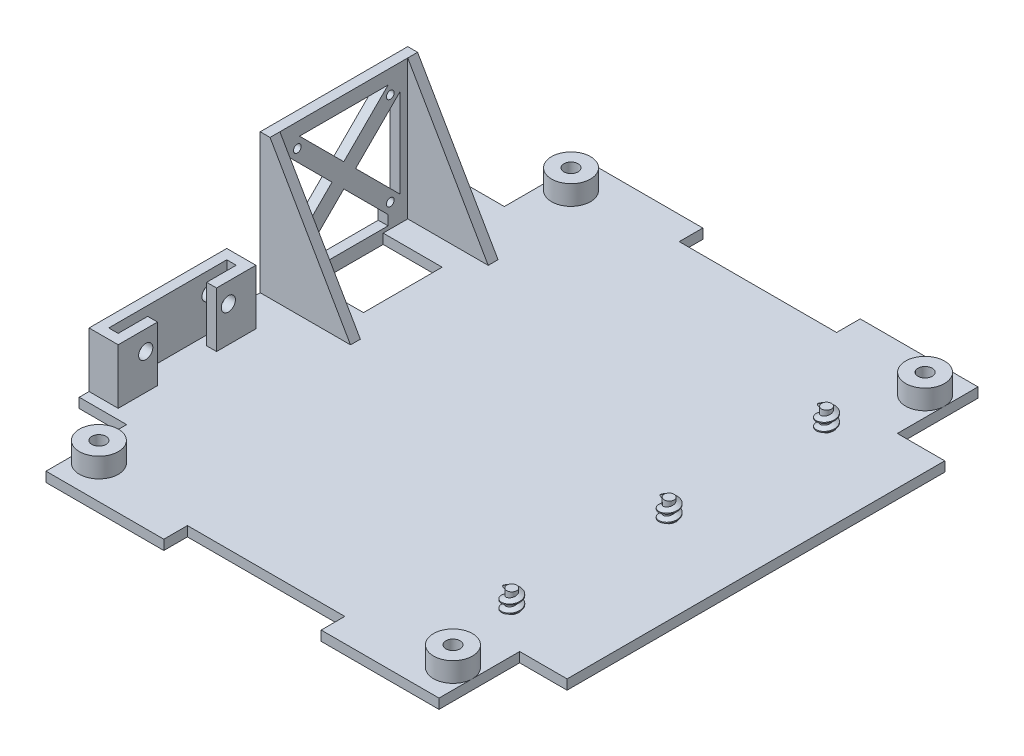
SolidWorks part; units mm, degrees
ref_plane "Front Plane" through (0, 0, 0) normal (0, 0, 1) x (1, 0, 0)
ref_plane "Top Plane" through (0, 0, 0) normal (0, 1, 0) x (1, 0, 0)
ref_plane "Right Plane" through (0, 0, 0) normal (1, 0, 0) x (0, 0, -1)
sketch "Sketch1" plane through (0, 0, 0) normal (0, 1, 0) x (1, 0, 0)
  line L0 (-25.4, 86.995) -> (-63.4314, 86.995)
  line L1 (-88.9, -101.6) -> (88.9, -101.6) construction
  line L2 (101.6, -88.9) -> (101.6, 88.9) construction
  line L3 (88.9, 101.6) -> (-88.9, 101.6) construction
  line L4 (-78.74, -60.96) -> (-63.4314, -60.96)
  line L5 (-63.4314, -60.96) -> (-63.4314, -86.995)
  line L6 (-63.4314, -86.995) -> (-25.4, -86.995)
  line L7 (63.4314, -86.995) -> (63.4314, -60.96)
  line L8 (63.4314, -60.96) -> (78.74, -60.96)
  line L9 (78.74, -60.96) -> (78.74, -25.4)
  line L10 (78.74, 60.96) -> (63.4314, 60.96)
  line L11 (63.4314, 60.96) -> (63.4314, 86.995)
  line L12 (63.4314, 86.995) -> (25.4, 86.995)
  line L13 (-63.4314, 86.995) -> (-63.4314, 60.96)
  line L14 (-63.4314, 60.96) -> (-78.74, 60.96)
  line L15 (-78.74, 60.96) -> (-78.74, 25.4)
  line L16 (-78.74, -25.4) -> (-78.74, -60.96)
  line L17 (-78.74, -25.4) -> (-71.12, -25.4)
  line L19 (-78.74, 25.4) -> (-71.12, 25.4)
  line L20 (-71.12, -25.4) -> (-71.12, 25.4)
  line L22 (-25.4, 86.995) -> (-25.4, 79.375)
  line L23 (-25.4, 79.375) -> (25.4, 79.375)
  line L24 (25.4, 86.995) -> (25.4, 79.375)
  line L25 (78.74, 25.4) -> (71.12, 25.4)
  line L27 (78.74, -25.4) -> (71.12, -25.4)
  line L28 (71.12, 25.4) -> (71.12, -25.4)
  line L30 (25.4, -86.995) -> (25.4, -79.375)
  line L31 (25.4, -79.375) -> (-25.4, -79.375)
  line L32 (-25.4, -86.995) -> (-25.4, -79.375)
  line L33 (78.74, 25.4) -> (78.74, 60.96)
  line L34 (25.4, -86.995) -> (63.4314, -86.995)
  line L35 (-101.6, 88.9) -> (-101.6, -88.9) construction
  arc A0 (88.9, -101.6) -> (101.6, -88.9) centre (88.9, -88.9) ccw construction
  arc A1 (-101.6, -88.9) -> (-88.9, -101.6) centre (-88.9, -88.9) ccw construction
  arc A2 (101.6, 88.9) -> (88.9, 101.6) centre (88.9, 88.9) ccw construction
  arc A3 (-101.6, 88.9) -> (-88.9, 101.6) centre (-88.9, 88.9) cw construction
  circle A4 centre (-57.15, 76.2) radius 2.286
  circle A5 centre (57.15, 76.2) radius 2.286
  circle A6 centre (57.15, -76.2) radius 2.286
  circle A7 centre (-57.15, -76.2) radius 2.286
  point P3 (0, 101.6)
  point P5 (101.6, 0)
  point P13 (101.6, 101.6)
  point P16 (-101.6, 101.6)
  point P38 (-71.12, 0)
  point P55 (0, -79.375)
  point P56 (0, 79.375)
  point P57 (71.12, 0)
  dimension "D2" = 12.7
  dimension "D11" = 4.572
  dimension "D8" = 44.45
  dimension "D1" = 203.2
  dimension "D3" = 203.2
  dimension "D4" = 22.86
  dimension "D5" = 15.3086
  dimension "D6" = 35.56
  dimension "D7" = 173.99
  dimension "D12" = 50.8
  dimension "D13" = 25.4
  dimension "D14" = 44.45
  dimension "D15" = 25.4
  dimension "D18" = 7.62
extrude "Main Body" add sketch "Sketch1" along normal blind 3.175
sketch "Sketch34" plane through (0, 3.175, 0) normal (0, 1, 0) x (1, 0, 0)
  line L0 (78.74, 25.4) -> (78.74, -25.4)
  line L1 (-78.74, 25.4) -> (-78.74, -25.4)
  line L28 (-78.74, -25.4) -> (-78.74, -60.96)
  line L29 (-78.74, -60.96) -> (-63.4314, -60.96)
  line L30 (-63.4314, -60.96) -> (-63.4314, -86.995)
  line L31 (-63.4314, -86.995) -> (-25.4, -86.995)
  line L32 (-25.4, -86.995) -> (-25.4, -79.375)
  line L33 (-25.4, -79.375) -> (25.4, -79.375)
  line L34 (25.4, -79.375) -> (25.4, -86.995)
  line L35 (25.4, -86.995) -> (63.4314, -86.995)
  line L36 (63.4314, -86.995) -> (63.4314, -60.96)
  line L37 (63.4314, -60.96) -> (78.74, -60.96)
  line L38 (78.74, -60.96) -> (78.74, -25.4)
  line L39 (78.74, -25.4) -> (71.12, -25.4)
  line L40 (71.12, -25.4) -> (71.12, 25.4)
  line L41 (71.12, 25.4) -> (78.74, 25.4)
  line L42 (78.74, 25.4) -> (78.74, 60.96)
  line L43 (78.74, 60.96) -> (63.4314, 60.96)
  line L44 (63.4314, 60.96) -> (63.4314, 86.995)
  line L45 (63.4314, 86.995) -> (25.4, 86.995)
  line L46 (25.4, 86.995) -> (25.4, 79.375)
  line L47 (25.4, 79.375) -> (-25.4, 79.375)
  line L48 (-25.4, 79.375) -> (-25.4, 86.995)
  line L49 (-25.4, 86.995) -> (-63.4314, 86.995)
  line L50 (-63.4314, 86.995) -> (-63.4314, 60.96)
  line L51 (-63.4314, 60.96) -> (-78.74, 60.96)
  line L52 (-78.74, 60.96) -> (-78.74, 25.4)
  line L53 (-78.74, 25.4) -> (-71.12, 25.4)
  line L54 (-71.12, 25.4) -> (-71.12, -25.4)
  line L55 (-71.12, -25.4) -> (-78.74, -25.4)
  line L56 (-78.74, -25.4) -> (-78.74, -60.96)
  line L57 (-78.74, -60.96) -> (-63.4314, -60.96)
  line L58 (-63.4314, -60.96) -> (-63.4314, -86.995)
  line L59 (-63.4314, -86.995) -> (-25.4, -86.995)
  line L60 (-25.4, -86.995) -> (-25.4, -79.375)
  line L61 (-25.4, -79.375) -> (25.4, -79.375)
  line L62 (25.4, -79.375) -> (25.4, -86.995)
  line L63 (25.4, -86.995) -> (63.4314, -86.995)
  line L64 (63.4314, -86.995) -> (63.4314, -60.96)
  line L65 (63.4314, -60.96) -> (78.74, -60.96)
  line L66 (78.74, -60.96) -> (78.74, -25.4)
  line L67 (78.74, -25.4) -> (71.12, -25.4)
  line L68 (71.12, -25.4) -> (71.12, 25.4)
  line L69 (71.12, 25.4) -> (78.74, 25.4)
  line L70 (78.74, 25.4) -> (78.74, 60.96)
  line L71 (78.74, 60.96) -> (63.4314, 60.96)
  line L72 (63.4314, 60.96) -> (63.4314, 86.995)
  line L73 (63.4314, 86.995) -> (25.4, 86.995)
  line L74 (25.4, 86.995) -> (25.4, 79.375)
  line L75 (25.4, 79.375) -> (-25.4, 79.375)
  line L76 (-25.4, 79.375) -> (-25.4, 86.995)
  line L77 (-25.4, 86.995) -> (-63.4314, 86.995)
  line L78 (-63.4314, 86.995) -> (-63.4314, 60.96)
  line L79 (-63.4314, 60.96) -> (-78.74, 60.96)
  line L80 (-78.74, 60.96) -> (-78.74, 25.4)
  line L81 (-78.74, 25.4) -> (-71.12, 25.4)
  line L82 (-71.12, 25.4) -> (-71.12, -25.4)
  line L83 (-71.12, -25.4) -> (-78.74, -25.4)
  line M42 (78.74, -25.4) -> (71.12, -25.4)
  line M43 (71.12, -25.4) -> (71.12, 25.4)
  line M44 (71.12, 25.4) -> (78.74, 25.4)
  line M56 (-78.74, 25.4) -> (-71.12, 25.4)
  line M57 (-71.12, 25.4) -> (-71.12, -25.4)
  line M58 (-71.12, -25.4) -> (-78.74, -25.4)
  dimension "D1" = 0
extrude "Boss-Extrude3" add sketch "Sketch34" against normal up to surface (3.175 mm away) contours L1 M56 M58 M57 | L0 M44 M43 M42 up to face at (0, 0, 0)
sketch "Sketch3" plane through (0, 3.175, 0) normal (0, 1, 0) x (1, 0, 0)
  line L0 (50.7314, -50.8) -> (50.7314, 50.8) construction
  line L28 (-78.74, 60.96) -> (-78.74, -60.96)
  line L29 (-78.74, -60.96) -> (-63.4314, -60.96)
  line L30 (-63.4314, -60.96) -> (-63.4314, -86.995)
  line L31 (-63.4314, -86.995) -> (-25.4, -86.995)
  line L32 (-25.4, -86.995) -> (-25.4, -79.375)
  line L33 (-25.4, -79.375) -> (25.4, -79.375)
  line L34 (25.4, -79.375) -> (25.4, -86.995)
  line L35 (25.4, -86.995) -> (63.4314, -86.995)
  line L36 (63.4314, -86.995) -> (63.4314, -60.96)
  line L37 (63.4314, -60.96) -> (78.74, -60.96)
  line L38 (78.74, -60.96) -> (78.74, 60.96)
  line L43 (78.74, 60.96) -> (63.4314, 60.96)
  line L44 (63.4314, 60.96) -> (63.4314, 86.995)
  line L45 (63.4314, 86.995) -> (25.4, 86.995)
  line L46 (25.4, 86.995) -> (25.4, 79.375)
  line L47 (25.4, 79.375) -> (-25.4, 79.375)
  line L48 (-25.4, 79.375) -> (-25.4, 86.995)
  line L49 (-25.4, 86.995) -> (-63.4314, 86.995)
  line L50 (-63.4314, 86.995) -> (-63.4314, 60.96)
  line L51 (-63.4314, 60.96) -> (-78.74, 60.96)
  line L56 (-78.74, 60.96) -> (-78.74, -60.96)
  line L57 (-78.74, -60.96) -> (-63.4314, -60.96)
  line L58 (-63.4314, -60.96) -> (-63.4314, -86.995)
  line L59 (-63.4314, -86.995) -> (-25.4, -86.995)
  line L60 (-25.4, -86.995) -> (-25.4, -79.375)
  line L61 (-25.4, -79.375) -> (25.4, -79.375)
  line L62 (25.4, -79.375) -> (25.4, -86.995)
  line L63 (25.4, -86.995) -> (63.4314, -86.995)
  line L64 (63.4314, -86.995) -> (63.4314, -60.96)
  line L65 (63.4314, -60.96) -> (78.74, -60.96)
  line L66 (78.74, -60.96) -> (78.74, 60.96)
  line L71 (78.74, 60.96) -> (63.4314, 60.96)
  line L72 (63.4314, 60.96) -> (63.4314, 86.995)
  line L73 (63.4314, 86.995) -> (25.4, 86.995)
  line L74 (25.4, 86.995) -> (25.4, 79.375)
  line L75 (25.4, 79.375) -> (-25.4, 79.375)
  line L76 (-25.4, 79.375) -> (-25.4, 86.995)
  line L77 (-25.4, 86.995) -> (-63.4314, 86.995)
  line L78 (-63.4314, 86.995) -> (-63.4314, 60.96)
  line L79 (-63.4314, 60.96) -> (-78.74, 60.96)
  circle A0 centre (50.7314, 50.8) radius 1.5875
  circle A1 centre (50.7314, 0) radius 1.5875
  circle A2 centre (50.7314, -50.8) radius 1.5875
  dimension "D2" = 3.175
  dimension "D5" = 101.6
  dimension "D6" = 12.7
  dimension "D1" = 0
extrude "Boss-Extrude2" add sketch "Sketch3" along normal blind 6.35 contours A0 | A1 | A2
thread "Thread1" pitch 2.54 method extrude trim with end face yes profile "Thread Profile1" start angle 0, offset 0, length 0, pitch 2.54, diameter 3.175
ref_plane "Plane1" through (49.1439, 9.525, -50.8) normal (0, 0, 1) x (-1, 0, 0)
sketch "Thread Profile1" plane through (49.1439, 9.525, -50.8) normal (0, 0, 1) x (-1, 0, 0)
  line L0 (0, 0) -> (0, 2.54) construction
  line L1 (0, 0) -> (1.3748, 0.7937)
  line L2 (1.3748, 0.7937) -> (1.3748, 1.1112)
  line L3 (1.3748, 1.1112) -> (0, 1.905)
  line L4 (1.3748, 0.9525) -> (0, 0.9525) construction
  line L11 (0, 0) -> (0, 1.905)
  point P2 (0, 0)
  dimension "Pitch" = 2.54
  dimension "Profile_Angle" = 60
  dimension "Profile_Land" = 0.3175
  dimension "Profile_Height" = 1.3748
thread "Thread2" pitch 2.54 method extrude trim with end face yes profile "Thread Profile3" start angle 0, offset 0, length 0, pitch 2.54, diameter 3.175
ref_plane "Plane3" through (49.1439, 9.525, 0) normal (0, 0, 1) x (-1, 0, 0)
sketch "Thread Profile3" plane through (49.1439, 9.525, 0) normal (0, 0, 1) x (-1, 0, 0)
  line L0 (0, 0) -> (0, 2.54) construction
  line L1 (0, 0) -> (1.3748, 0.7937)
  line L2 (1.3748, 0.7937) -> (1.3748, 1.1112)
  line L3 (1.3748, 1.1112) -> (0, 1.905)
  line L4 (1.3748, 0.9525) -> (0, 0.9525) construction
  line L11 (0, 0) -> (0, 1.905)
  point P2 (0, 0)
  dimension "Pitch" = 2.54
  dimension "Profile_Angle" = 60
  dimension "Profile_Land" = 0.3175
  dimension "Profile_Height" = 1.3748
thread "Thread3" pitch 2.54 method extrude trim with end face yes profile "Thread Profile4" start angle 0, offset 0, length 0, pitch 2.54, diameter 3.175
ref_plane "Plane4" through (49.1439, 9.525, 50.8) normal (0, 0, 1) x (-1, 0, 0)
sketch "Thread Profile4" plane through (49.1439, 9.525, 50.8) normal (0, 0, 1) x (-1, 0, 0)
  line L0 (0, 0) -> (0, 2.54) construction
  line L1 (0, 0) -> (1.3748, 0.7937)
  line L2 (1.3748, 0.7937) -> (1.3748, 1.1112)
  line L3 (1.3748, 1.1112) -> (0, 1.905)
  line L4 (1.3748, 0.9525) -> (0, 0.9525) construction
  line L11 (0, 0) -> (0, 1.905)
  point P2 (0, 0)
  dimension "Pitch" = 2.54
  dimension "Profile_Angle" = 60
  dimension "Profile_Land" = 0.3175
  dimension "Profile_Height" = 1.3748
sketch "Sketch35" plane through (0, 3.175, 0) normal (0, 1, 0) x (1, 0, 0)
  line L20 (-78.74, 60.96) -> (-78.74, -60.96)
  line L21 (-78.74, -60.96) -> (-63.4314, -60.96)
  line L22 (-63.4314, -60.96) -> (-63.4314, -86.995)
  line L23 (-63.4314, -86.995) -> (-25.4, -86.995)
  line L24 (-25.4, -86.995) -> (-25.4, -79.375)
  line L25 (-25.4, -79.375) -> (25.4, -79.375)
  line L26 (25.4, -79.375) -> (25.4, -86.995)
  line L27 (25.4, -86.995) -> (63.4314, -86.995)
  line L28 (63.4314, -86.995) -> (63.4314, -60.96)
  line L29 (63.4314, -60.96) -> (78.74, -60.96)
  line L30 (78.74, -60.96) -> (78.74, 60.96)
  line L31 (78.74, 60.96) -> (63.4314, 60.96)
  line L32 (63.4314, 60.96) -> (63.4314, 86.995)
  line L33 (63.4314, 86.995) -> (25.4, 86.995)
  line L34 (25.4, 86.995) -> (25.4, 79.375)
  line L35 (25.4, 79.375) -> (-25.4, 79.375)
  line L36 (-25.4, 79.375) -> (-25.4, 86.995)
  line L37 (-25.4, 86.995) -> (-63.4314, 86.995)
  line L38 (-63.4314, 86.995) -> (-63.4314, 60.96)
  line L39 (-63.4314, 60.96) -> (-78.74, 60.96)
  line L40 (-78.74, 60.96) -> (-78.74, -60.96)
  line L41 (-78.74, -60.96) -> (-63.4314, -60.96)
  line L42 (-63.4314, -60.96) -> (-63.4314, -86.995)
  line L43 (-63.4314, -86.995) -> (-25.4, -86.995)
  line L44 (-25.4, -86.995) -> (-25.4, -79.375)
  line L45 (-25.4, -79.375) -> (25.4, -79.375)
  line L46 (25.4, -79.375) -> (25.4, -86.995)
  line L47 (25.4, -86.995) -> (63.4314, -86.995)
  line L48 (63.4314, -86.995) -> (63.4314, -60.96)
  line L49 (63.4314, -60.96) -> (78.74, -60.96)
  line L50 (78.74, -60.96) -> (78.74, 60.96)
  line L51 (78.74, 60.96) -> (63.4314, 60.96)
  line L52 (63.4314, 60.96) -> (63.4314, 86.995)
  line L53 (63.4314, 86.995) -> (25.4, 86.995)
  line L54 (25.4, 86.995) -> (25.4, 79.375)
  line L55 (25.4, 79.375) -> (-25.4, 79.375)
  line L56 (-25.4, 79.375) -> (-25.4, 86.995)
  line L57 (-25.4, 86.995) -> (-63.4314, 86.995)
  line L58 (-63.4314, 86.995) -> (-63.4314, 60.96)
  line L59 (-63.4314, 60.96) -> (-78.74, 60.96)
  circle A0 centre (-57.15, 76.2) radius 2.286 construction
  circle A1 centre (-57.15, -76.2) radius 2.286 construction
  circle A2 centre (57.15, -76.2) radius 2.286 construction
  circle A3 centre (57.15, 76.2) radius 2.286 construction
  circle A4 centre (-57.15, 76.2) radius 2.286
  circle A5 centre (-57.15, -76.2) radius 2.286
  circle A6 centre (57.15, -76.2) radius 2.286
  circle A7 centre (57.15, 76.2) radius 2.286
  circle A8 centre (-57.15, 76.2) radius 6.2814
  circle A9 centre (-57.15, -76.2) radius 6.2814
  circle A10 centre (57.15, -76.2) radius 6.2814
  circle A11 centre (57.15, 76.2) radius 6.2814
  circle M21 centre (57.15, -76.2) radius 2.286
  circle M22 centre (-57.15, 76.2) radius 2.286
  circle M43 centre (57.15, 76.2) radius 2.286
  circle M44 centre (-57.15, -76.2) radius 2.286
  dimension "D1" = 0
extrude "Boss-Extrude4" add sketch "Sketch35" along normal blind 6.35 contours A11 M43 | A10 M21 | A9 M44 | A8 M22
sketch "Sketch36" plane through (0, 3.175, 0) normal (0, 1, 0) x (1, 0, 0)
  line L0 (-78.2696, -45.212) -> (-78.2696, -40.64)
  line L1 (-70.6496, -48.26) -> (-78.2696, -45.212)
  line L2 (-63.4314, 60.96) -> (-78.74, 60.96) construction
  line L3 (-78.74, 60.96) -> (-78.74, -60.96) construction
  line L4 (-78.74, -60.96) -> (-63.4314, -60.96) construction
  line L5 (-66.8396, -48.26) -> (-70.6496, -48.26)
  line L6 (-59.2196, -45.212) -> (-66.8396, -48.26)
  line L7 (-59.2196, -40.64) -> (-59.2196, -45.212)
  line L96 (-78.74, -60.96) -> (-63.4314, -60.96)
  line L97 (-78.74, 60.96) -> (-78.74, -60.96)
  line L98 (-63.4314, 60.96) -> (-78.74, 60.96)
  line L99 (-78.2696, -31.115) -> (-59.2196, -31.115) construction
  line L100 (-78.2696, -21.59) -> (-59.2196, -21.59)
  line L101 (-78.2696, -21.59) -> (-78.2696, -40.64)
  line L102 (-78.2696, -40.64) -> (-59.2196, -40.64)
  line L103 (-59.2196, -21.59) -> (-59.2196, -40.64)
  line L104 (-78.2696, -21.59) -> (-59.2196, -40.64) construction
  line L105 (-78.2696, -40.64) -> (-59.2196, -21.59) construction
  line L106 (-59.2196, -21.59) -> (-59.2196, -17.018)
  line L107 (-59.2196, -17.018) -> (-66.8396, -13.97)
  line L108 (-66.8396, -13.97) -> (-70.6496, -13.97)
  line L109 (-70.6496, -13.97) -> (-78.2696, -17.018)
  line L110 (-78.2696, -17.018) -> (-78.2696, -21.59)
  circle A0 centre (-68.7446, -17.78) radius 2.286
  circle A1 centre (-68.7446, -44.45) radius 2.286
  point P0 (-68.7446, -31.115)
  dimension "D6" = 4.572
  dimension "D1" = 19.05
  dimension "D2" = 4.572
  dimension "D3" = 7.62
  dimension "D4" = 3.81
  dimension "D5" = 3.81
  dimension "D7" = 12.7
  dimension "D8" = 0.4704
sketch "Sketch37" plane through (0, 3.175, 0) normal (0, 1, 0) x (1, 0, 0)
  line L2 (-63.4314, 60.96) -> (-78.74, 60.96) construction
  line L3 (-78.74, 60.96) -> (-78.74, -60.96) construction
  line L24 (-78.74, 60.96) -> (-78.74, -60.96)
  line L25 (-63.4314, 60.96) -> (-78.74, 60.96)
  line L27 (-78.74, 45.085) -> (-75.565, 45.085)
  line L28 (-78.74, 45.085) -> (-78.74, -2.54)
  line L29 (-78.74, -2.54) -> (-75.565, -2.54)
  line L30 (-75.565, 45.085) -> (-75.565, -2.54)
  dimension "D1" = 3.175
  dimension "D2" = 47.625
  dimension "D3" = 15.875
extrude "Boss-Extrude5" add sketch "Sketch37" along normal blind 45 contours L30 L27 L24 L29
sketch "Sketch38" plane through (0, 0, -45.085) normal (0, 0, -1) x (-1, 0, 0)
  line L0 (75.565, 48.175) -> (49.5842, 3.175)
  line L1 (25.4, 3.175) -> (63.4314, 3.175) construction
  line L2 (49.5842, 3.175) -> (75.565, 3.175)
  line L4 (75.565, 3.175) -> (78.74, 3.175)
  line L5 (78.74, 3.175) -> (78.74, 48.175)
  line L6 (78.74, 48.175) -> (75.565, 48.175)
  line L7 (75.565, 48.175) -> (75.565, 3.175)
  line L8 (75.565, 3.175) -> (78.74, 3.175)
  line L9 (78.74, 3.175) -> (78.74, 48.175)
  line L10 (78.74, 48.175) -> (75.565, 48.175)
  line L11 (75.565, 48.175) -> (75.565, 3.175)
  line M9 (75.565, 48.175) -> (75.565, 3.175)
  dimension "D2" = 30
  dimension "D1" = 0
extrude "Boss-Extrude6" add sketch "Sketch38" against normal blind 3.175 contours L0 L2 M9
sketch "Sketch39" plane through (0, 0, 2.54) normal (0, 0, 1) x (1, 0, 0)
  line L0 (-75.565, 48.175) -> (-49.5842, 3.175)
  line L1 (-49.5842, 3.175) -> (-75.565, 3.175)
  line L4 (-78.74, 3.175) -> (-75.565, 3.175)
  line L5 (-75.565, 3.175) -> (-75.565, 48.175)
  line L6 (-75.565, 48.175) -> (-78.74, 48.175)
  line L7 (-78.74, 48.175) -> (-78.74, 3.175)
  line L8 (-78.74, 3.175) -> (-75.565, 3.175)
  line L9 (-75.565, 3.175) -> (-75.565, 48.175)
  line L10 (-75.565, 48.175) -> (-78.74, 48.175)
  line L11 (-78.74, 48.175) -> (-78.74, 3.175)
  line M7 (-75.565, 3.175) -> (-75.565, 48.175)
  dimension "D2" = 30
  dimension "D1" = 0
extrude "Boss-Extrude7" add sketch "Sketch39" against normal blind 3.175 contours L1 L0 M7
sketch "Sketch40" plane through (-78.74, 0, 0) normal (-1, 0, 0) x (0, 0, 1)
  line L0 (-35.56, 43.7725) -> (-6.985, 43.7725)
  line L1 (-40.2725, 6.675) -> (-2.2725, 6.675)
  line L2 (-40.2725, 6.675) -> (-40.2725, 44.675)
  line L3 (-40.2725, 44.675) -> (-2.2725, 44.675)
  line L4 (-2.2725, 6.675) -> (-2.2725, 44.675)
  line L5 (-40.2725, 6.675) -> (-2.2725, 44.675) construction
  line L6 (-40.2725, 44.675) -> (-2.2725, 6.675) construction
  line L7 (-6.985, 43.7725) -> (-21.2725, 29.485)
  line L8 (-60.96, 0) -> (60.96, 0)
  line L9 (60.96, 0) -> (60.96, 3.175)
  line L10 (60.96, 3.175) -> (2.54, 3.175)
  line L11 (2.54, 3.175) -> (2.54, 48.175)
  line L12 (2.54, 48.175) -> (-45.085, 48.175)
  line L13 (-45.085, 48.175) -> (-45.085, 3.175)
  line L14 (-45.085, 3.175) -> (-60.96, 3.175)
  line L15 (-60.96, 3.175) -> (-60.96, 0)
  line L16 (-60.96, 0) -> (60.96, 0)
  line L17 (60.96, 0) -> (60.96, 3.175)
  line L18 (60.96, 3.175) -> (2.54, 3.175)
  line L19 (2.54, 3.175) -> (2.54, 48.175)
  line L20 (2.54, 48.175) -> (-45.085, 48.175)
  line L21 (-45.085, 48.175) -> (-45.085, 3.175)
  line L22 (-45.085, 3.175) -> (-60.96, 3.175)
  line L23 (-60.96, 3.175) -> (-60.96, 0)
  line L24 (-21.2725, 29.485) -> (-35.56, 43.7725)
  line L25 (-17.4625, 25.675) -> (-3.175, 39.9625)
  line L26 (-3.175, 39.9625) -> (-3.175, 11.3875)
  line L27 (-3.175, 11.3875) -> (-17.4625, 25.675)
  line L28 (-21.2725, 21.865) -> (-6.985, 7.5775)
  line L29 (-6.985, 7.5775) -> (-35.56, 7.5775)
  line L30 (-35.56, 7.5775) -> (-21.2725, 21.865)
  line L31 (-25.0825, 25.675) -> (-39.37, 11.3875)
  line L32 (-39.37, 11.3875) -> (-39.37, 39.9625)
  line L33 (-39.37, 39.9625) -> (-25.0825, 25.675)
  circle A0 centre (-36.2725, 40.675) radius 1.25
  circle A1 centre (-6.2725, 40.675) radius 1.25
  circle A2 centre (-6.2725, 10.675) radius 1.25
  circle A3 centre (-36.2725, 10.675) radius 1.25
  point P2 (-45.085, 25.675)
  point P4 (-21.2725, 48.175)
  point P6 (-21.2725, 25.675)
  point P15 (-6.2725, 40.675)
  point P16 (-6.2725, 10.675)
  point P17 (-36.2725, 40.675)
  point P18 (-36.2725, 10.675)
  point P29 (-21.2725, 43.7725)
  point P43 (-21.2725, 25.675)
  dimension "D4" = 2.5
  dimension "D2" = 38
  dimension "D3" = 4
  dimension "D5" = 28.575
  dimension "D6" = 3.81
  dimension "D7" = 45
  dimension "D8" = 4
  dimension "D1" = 0
extrude "Cut-Extrude3" cut sketch "Sketch40" against normal up to surface (3.175 mm away) contours L25 L26 L27 | L28 L29 L30 | A2 | A3 | L31 L32 L33 | L7 L24 L0 | A1 | A0 up to face at (-75.565, 25.675, -21.2725)
sketch "Sketch41" plane through (0, 3.175, 0) normal (0, 1, 0) x (1, 0, 0)
  line L0 (-75.565, 41.91) -> (-75.565, 0.635) construction
  line L31 (-49.5842, 41.91) -> (-75.565, 41.91) construction
  line L32 (-49.5842, 0.635) -> (-75.565, 0.635) construction
  line L33 (-49.5842, 0.635) -> (-75.565, 0.635)
  line L34 (-75.565, 41.91) -> (-75.565, 0.635)
  line L35 (-49.5842, 41.91) -> (-75.565, 41.91)
  line L37 (-75.565, 8.5725) -> (-56.515, 8.5725)
  line L38 (-75.565, 8.5725) -> (-75.565, 33.9725)
  line L39 (-75.565, 33.9725) -> (-56.515, 33.9725)
  line L40 (-56.515, 8.5725) -> (-56.515, 33.9725)
  point P7 (-75.565, 21.2725)
  point P8 (-56.515, 21.2725)
  dimension "D1" = 19.05
  dimension "D2" = 25.4
extrude "Cut-Extrude4" cut sketch "Sketch41" against normal up to next contours L37 L40 L39 L34
sketch "Sketch46" plane through (0, 3.175, 0) normal (0, 1, 0) x (1, 0, 0)
  line L1 (-69.342, -16.51) -> (-78.74, -16.51)
  line L2 (-69.342, -54.61) -> (-78.74, -54.61)
  line L3 (-69.342, -54.61) -> (-69.342, -57.785)
  line L4 (-69.342, -57.785) -> (-78.74, -57.785)
  line L5 (-78.74, -54.61) -> (-78.74, -57.785)
  line L6 (-69.342, -16.51) -> (-69.342, -13.335)
  line L7 (-69.342, -13.335) -> (-78.74, -13.335)
  line L8 (-78.74, -16.51) -> (-78.74, -13.335)
  line L36 (-78.74, -60.96) -> (-63.4314, -60.96) construction
  line L37 (-78.74, 60.96) -> (-78.74, -60.96) construction
  line L38 (-78.74, -60.96) -> (-63.4314, -60.96)
  line L39 (-78.74, 60.96) -> (-78.74, -60.96)
  line L41 (-72.517, -16.51) -> (-72.517, -26.035)
  line L42 (-78.74, -16.51) -> (-75.565, -16.51)
  line L43 (-78.74, -16.51) -> (-78.74, -54.61)
  line L44 (-78.74, -54.61) -> (-75.565, -54.61)
  line L45 (-75.565, -16.51) -> (-75.565, -54.61)
  line L46 (-72.517, -16.51) -> (-69.342, -16.51)
  line L48 (-72.517, -54.61) -> (-69.342, -54.61)
  line L50 (-72.517, -26.035) -> (-69.342, -26.035)
  line L51 (-69.342, -26.035) -> (-69.342, -16.51)
  line L52 (-72.517, -54.61) -> (-72.517, -45.085)
  line L53 (-72.517, -45.085) -> (-69.342, -45.085)
  line L54 (-69.342, -45.085) -> (-69.342, -54.61)
  point P15 (-72.517, -21.2725)
  point P16 (-72.517, -49.8475)
  dimension "D1" = 3.175
  dimension "D2" = 38.1
  dimension "D3" = 6.35
  dimension "D4" = 19.05
  dimension "D5" = 3.048
  dimension "D6" = 3.175
extrude "Boss-Extrude8" add sketch "Sketch46" along normal blind 17.78
sketch "Sketch47" plane through (-78.74, 0, 0) normal (-1, 0, 0) x (0, 0, 1)
  line L3 (45.085, 20.955) -> (45.085, 3.175) construction
  line L5 (26.035, 3.175) -> (26.035, 20.955) construction
  line L11 (45.085, 20.955) -> (45.085, 3.175)
  line L12 (-60.96, 0) -> (60.96, 0)
  line L13 (60.96, 0) -> (60.96, 3.175)
  line L14 (60.96, 3.175) -> (57.785, 3.175)
  line L15 (57.785, 3.175) -> (57.785, 20.955)
  line L16 (57.785, 20.955) -> (13.335, 20.955)
  line L18 (13.335, 3.175) -> (2.54, 3.175)
  line L19 (2.54, 3.175) -> (2.54, 48.175)
  line L20 (2.54, 48.175) -> (-45.085, 48.175)
  line L21 (-45.085, 48.175) -> (-45.085, 3.175)
  line L22 (-45.085, 3.175) -> (-60.96, 3.175)
  line L23 (-60.96, 3.175) -> (-60.96, 0)
  line L24 (-60.96, 0) -> (60.96, 0)
  line L25 (60.96, 0) -> (60.96, 3.175)
  line L26 (60.96, 3.175) -> (57.785, 3.175)
  line L30 (13.335, 3.175) -> (2.54, 3.175)
  line L31 (2.54, 3.175) -> (2.54, 48.175)
  line L32 (2.54, 48.175) -> (-45.085, 48.175)
  line L33 (-45.085, 48.175) -> (-45.085, 3.175)
  line L34 (-45.085, 3.175) -> (-60.96, 3.175)
  line L35 (-60.96, 3.175) -> (-60.96, 0)
  line L37 (26.035, 3.175) -> (26.035, 20.955)
  line L40 (22.225, 14.605) -> (48.895, 14.605) construction
  line L41 (13.335, 20.955) -> (57.785, 20.955) construction
  line L42 (26.035, 3.175) -> (45.085, 3.175) construction
  line L43 (13.335, 20.955) -> (57.785, 20.955)
  line L44 (13.335, 20.955) -> (13.335, 3.175) construction
  line L45 (57.785, 20.955) -> (57.785, 3.175) construction
  line L46 (13.335, 20.955) -> (13.335, 3.175)
  line L47 (57.785, 20.955) -> (57.785, 3.175)
  line L60 (13.335, 20.955) -> (13.335, 3.175)
  line L61 (13.335, 20.955) -> (13.335, 3.175)
  circle A0 centre (22.225, 14.605) radius 2.286
  circle A1 centre (48.895, 14.605) radius 2.286
  point P14 (35.56, 14.605)
  point P18 (0, 0)
  point P22 (35.56, 3.175)
  dimension "D2" = 4.572
  dimension "D3" = 26.67
  dimension "D4" = 11.43
  dimension "D1" = 0
extrude "Cut-Extrude5" cut sketch "Sketch47" against normal up to surface (9.398 mm away) contours A1 | A0 up to face at (-69.342, 12.065, 19.685)
sketch "Sketch48" plane through (-78.74, 0, 0) normal (-1, 0, 0) x (0, 0, 1)
  line L0 (-6.985, 7.5775) -> (-35.56, 7.5775) construction
  line L1 (-6.985, 7.5775) -> (-35.56, 7.5775)
  line L2 (-35.56, 7.5775) -> (-35.56, 4.4025)
  line L3 (-35.56, 4.4025) -> (-6.985, 4.4025)
  line L4 (-6.985, 4.4025) -> (-6.985, 7.5775)
  line L12 (-60.96, 0) -> (60.96, 0)
  line L13 (60.96, 0) -> (60.96, 3.175)
  line L14 (60.96, 3.175) -> (57.785, 3.175)
  line L15 (57.785, 3.175) -> (57.785, 20.955)
  line L16 (57.785, 20.955) -> (13.335, 20.955)
  line L17 (13.335, 20.955) -> (13.335, 3.175)
  line L18 (13.335, 3.175) -> (2.54, 3.175)
  line L19 (2.54, 3.175) -> (2.54, 48.175)
  line L20 (2.54, 48.175) -> (-45.085, 48.175)
  line L21 (-45.085, 48.175) -> (-45.085, 3.175)
  line L22 (-45.085, 3.175) -> (-60.96, 3.175)
  line L23 (-60.96, 3.175) -> (-60.96, 0)
  line L24 (-60.96, 0) -> (60.96, 0)
  line L25 (60.96, 0) -> (60.96, 3.175)
  line L26 (60.96, 3.175) -> (57.785, 3.175)
  line L27 (57.785, 3.175) -> (57.785, 20.955)
  line L28 (57.785, 20.955) -> (13.335, 20.955)
  line L29 (13.335, 20.955) -> (13.335, 3.175)
  line L30 (13.335, 3.175) -> (2.54, 3.175)
  line L31 (2.54, 3.175) -> (2.54, 48.175)
  line L32 (2.54, 48.175) -> (-45.085, 48.175)
  line L33 (-45.085, 48.175) -> (-45.085, 3.175)
  line L34 (-45.085, 3.175) -> (-60.96, 3.175)
  line L35 (-60.96, 3.175) -> (-60.96, 0)
  line M19 (-6.985, 7.5775) -> (-35.56, 7.5775)
  dimension "D2" = 3.175
  dimension "D1" = 0
extrude "Cut-Extrude6" cut sketch "Sketch48" against normal up to next contours L3 L4 L2 M19
